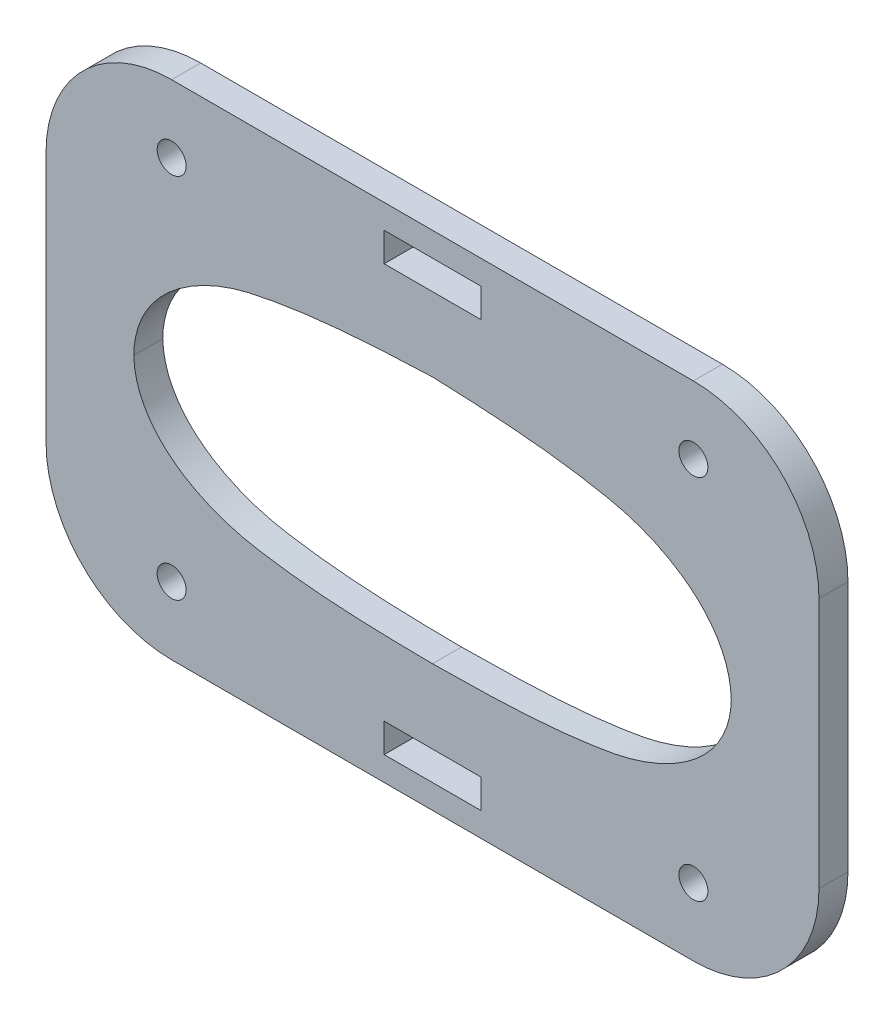
SolidWorks part; units mm, degrees
ref_plane "Plano frontal" through (0, 0, 0) normal (0, 0, 1) x (1, 0, 0)
ref_plane "Plano superior" through (0, 0, 0) normal (0, 1, 0) x (1, 0, 0)
ref_plane "Plano direito" through (0, 0, 0) normal (1, 0, 0) x (0, 0, -1)
sketch "Esboço1" plane through (0, 0, 0) normal (0, 0, 1) x (1, 0, 0)
  line L0 (40, 0.6746) -> (-40, 0.6746) construction
  line L5 (27, 26.6746) -> (-27, 26.6746)
  line L6 (40, 13.6746) -> (40, -12.3254)
  line L7 (27, -25.3254) -> (-27, -25.3254)
  line L8 (-40, 13.6746) -> (-40, -12.3254)
  line L13 (40, 26.6746) -> (-40, -25.3254) construction
  line L14 (40, -25.3254) -> (-40, 26.6746) construction
  line L27 (0, -12.1787) -> (0, 13.528) construction
  line L28 (30.9233, 0) -> (-30.9233, 0) construction
  line L29 (5, -22.8254) -> (-5, -22.8254)
  line L30 (5, -22.8254) -> (5, -19.8254)
  line L31 (5, -19.8254) -> (-5, -19.8254)
  line L32 (-5, -22.8254) -> (-5, -19.8254)
  line L33 (5, -22.8254) -> (-5, -19.8254) construction
  line L34 (5, -19.8254) -> (-5, -22.8254) construction
  line L35 (5, 21.1746) -> (-5, 24.1746) construction
  line L36 (5, 24.1746) -> (-5, 21.1746) construction
  line L37 (-5, 24.1746) -> (-5, 21.1746)
  line L38 (5, 21.1746) -> (-5, 21.1746)
  line L39 (5, 24.1746) -> (5, 21.1746)
  line L40 (5, 24.1746) -> (-5, 24.1746)
  line L41 (27, -25.3254) -> (27, 26.6746) construction
  line L42 (0, -25.3254) -> (0, 26.6746) construction
  arc A0 (-27, -25.3254) -> (-40, -12.3254) centre (-27, -12.3254) cw
  arc A1 (-27, 26.6746) -> (-40, 13.6746) centre (-27, 13.6746) ccw
  arc A2 (27, 26.6746) -> (40, 13.6746) centre (27, 13.6746) cw
  arc A3 (40, -12.3254) -> (27, -25.3254) centre (27, -12.3254) cw
  circle A4 centre (27, -18.3254) radius 1.5
  circle A5 centre (-27, -18.3254) radius 1.5
  circle A6 centre (27, 19.6746) radius 1.5
  circle A7 centre (-27, 19.6746) radius 1.5
  spline S0 degree 3 poles (0, 13.528) (-6.2445, 13.2882) (-12.519, 12.9674) (-24.7294, 10.3516) (-30.8289, 6.2917) (-30.9233, 0) knots 0 0 0 0 0.5 0.5 1 1 1 1
  spline S1 degree 3 poles (30.9233, 0) (30.7402, -6.1814) (24.461, -9.8549) (12.3346, -11.9845) (6.1556, -12.1121) (0, -12.1787) knots 0 0 0 0 0.5 0.5 1 1 1 1
  spline S2 degree 3 poles (0, 13.528) (6.2445, 13.2882) (12.519, 12.9674) (24.7294, 10.3516) (30.8289, 6.2917) (30.9233, 0) knots 0 0 0 0 0.5 0.5 1 1 1 1
  spline S3 degree 3 poles (-30.9233, 0) (-30.7402, -6.1814) (-24.461, -9.8549) (-12.3346, -11.9845) (-6.1556, -12.1121) (0, -12.1787) knots 0 0 0 0 0.5 0.5 1 1 1 1
  point P0 (0, 0)
  point P1 (0, 0.6746)
  point P6 (0, -21.3254)
  point P18 (0, 22.6746)
  dimension "D5" = 35
  dimension "D6" = 13
  dimension "D8" = 3
  dimension "D9" = 7
  dimension "D1" = 52
  dimension "D2" = 80
  dimension "D3" = 10
  dimension "D4" = 3
  dimension "D7" = 4
extrude "Ressalto-extrusão1" add sketch "Esboço1" along normal blind 3
